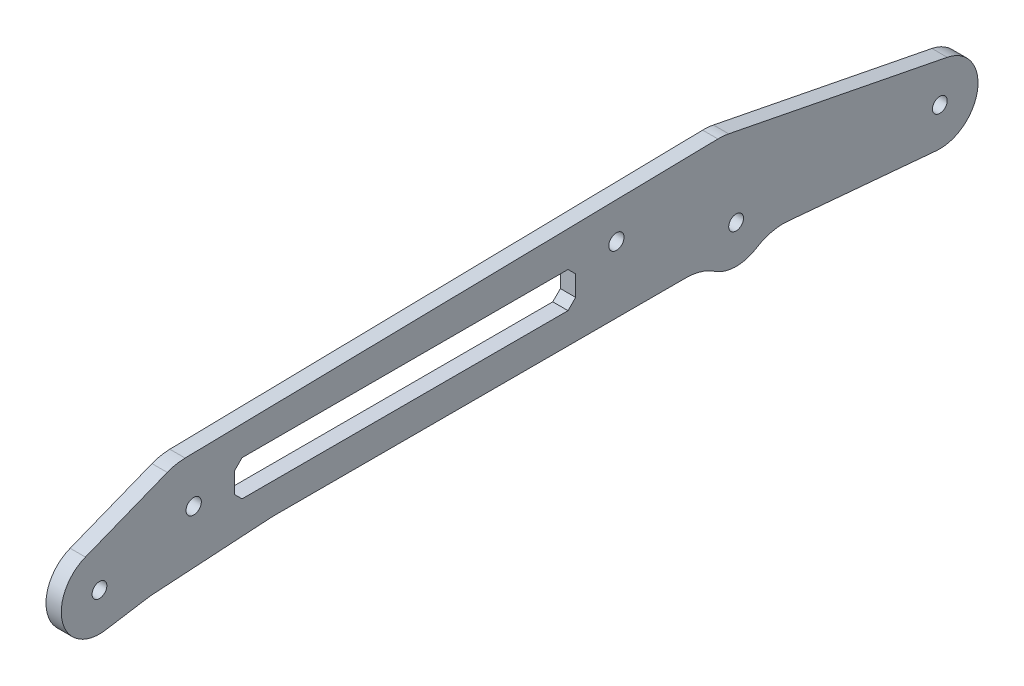
SolidWorks part; units mm, degrees
ref_plane "Front Plane" through (0, 0, 0) normal (0, 0, 1) x (1, 0, 0)
ref_plane "Top Plane" through (0, 0, 0) normal (0, 1, 0) x (1, 0, 0)
ref_plane "Right Plane" through (0, 0, 0) normal (1, 0, 0) x (0, 0, -1)
sketch "Sketch1" plane through (0, 0, 0) normal (1, 0, 0) x (0, 0, -1)
  line L0 (0, 0) -> (-125, 0) construction
  line L1 (-115, -6) -> (-91, -4.5)
  line L2 (-110, 14) -> (-2.5, 16)
  line L3 (-2.5, 16) -> (41.447, 7.3591)
  line L4 (39.3343, -7.4704) -> (6, -4.5)
  line L5 (-127.7591, 6.974) -> (-110, 14)
  line L6 (-115, -6) -> (-123.8188, -7.4064)
  line L7 (-91, -4.5) -> (-6, -4.5)
  line L8 (-56.25, 15) -> (-65, 5.5856) construction
  line L9 (-31.5, 7) -> (-33, 8.5)
  line L10 (-33, 8.5) -> (-97, 8.5)
  line L11 (-31.5, 7) -> (-31.5, 3)
  line L12 (-33, 1.5) -> (-97, 1.5)
  line L13 (-98.5, 7) -> (-98.5, 3)
  line L14 (-31.5, 3) -> (-33, 1.5)
  line L15 (-97, 8.5) -> (-98.5, 7)
  line L16 (-97, 1.5) -> (-98.5, 3)
  circle A0 centre (0, 0) radius 7.5
  circle A1 centre (-125, 0) radius 7.5
  circle A2 centre (40, 0) radius 7.5
  circle A3 centre (0, 0) radius 1.45
  circle A4 centre (-125, 0) radius 1.45
  circle A5 centre (40, 0) radius 1.45
  circle A8 centre (-106.5, 5) radius 1.5
  circle A9 centre (-23.5, 8.5) radius 1.5
  point P22 (-31.5, 8.5)
  point P23 (-98.5, 1.5)
  point P24 (-31.5, 1.5)
  point P25 (-98.5, 8.5)
  dimension "D1" = 15
  dimension "D3" = 15
  dimension "D4" = 15
  dimension "D5" = 2.9
  dimension "D7" = 15
  dimension "D9" = 40
  dimension "D10" = 2.5
  dimension "D6" = 10
  dimension "D13" = 6
  dimension "D14" = 4.5
  dimension "D18" = 8
  dimension "D19" = 3
  dimension "D20" = 5
  dimension "D21" = 18.5
  dimension "D23" = 23.5
  dimension "D24" = 8.5
  dimension "D2" = 125
  dimension "D8" = 14
  dimension "D11" = 16
  dimension "D12" = 4.5
  dimension "D15" = 85
  dimension "D16" = 7
  dimension "D17" = 6
  dimension "D22" = 8.75
  dimension "D25" = 8
extrude "Boss-Extrude1" add sketch "Sketch1" along normal mid plane 3 contours A2 A5 | A3 A0 | A1 A4 | L0 A0 L4 A2 L3 L2 L5 A1 | A0 L0 A1 L6 L1 L7 region at (0, -6.5345, 119.4363) region at (0, -1.9259, 132.0288) region at (0, 6.9139, 2.3046) region at (0, 1.0279, -32.785)
fillet "Fillet1" radius 10 6 edges at (0, -4.5, 91) (0, -6, 115) (0, 16, 2.5) (0, -4.5, -6) (0, -4.5, 6) (0, 14, 110)
